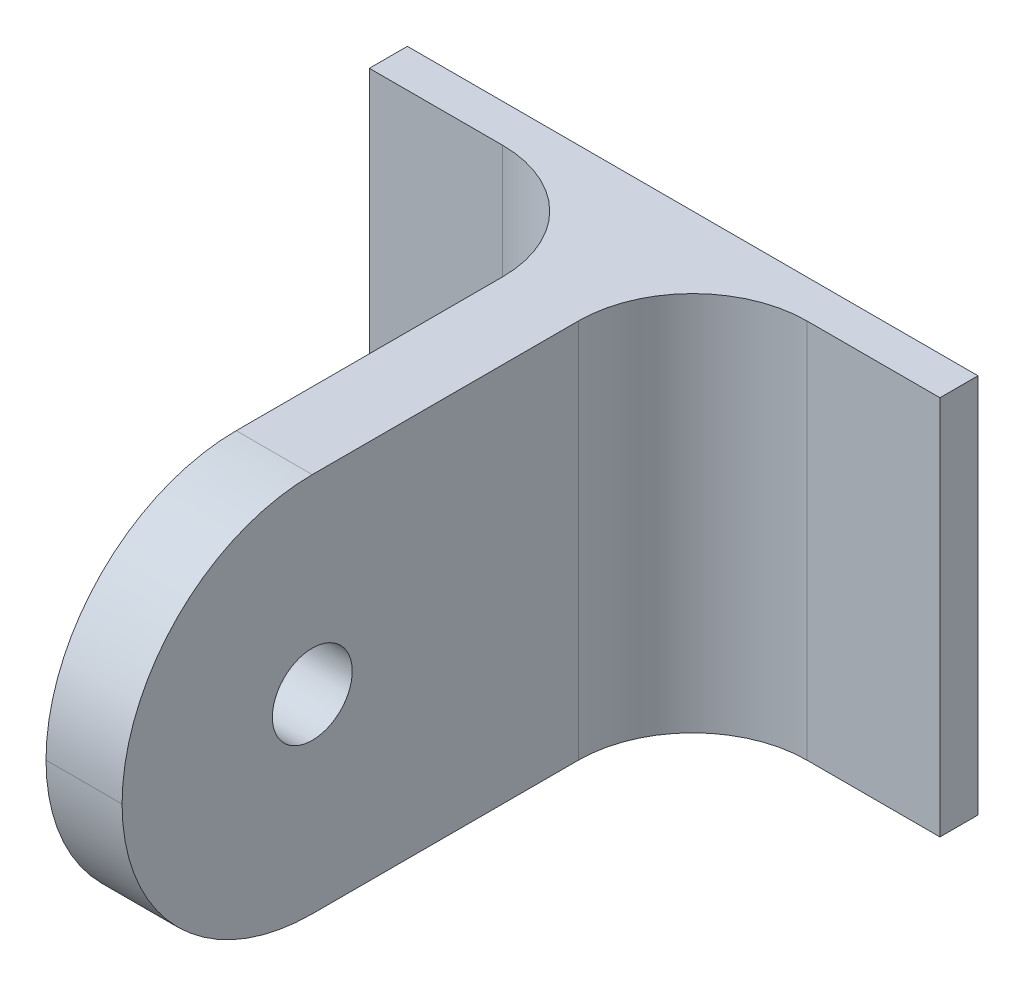
SolidWorks part; units mm, degrees
ref_plane "前视基准面" through (0, 0, 0) normal (0, 0, 1) x (1, 0, 0)
ref_plane "上视基准面" through (0, 0, 0) normal (0, 1, 0) x (1, 0, 0)
ref_plane "右视基准面" through (0, 0, 0) normal (1, 0, 0) x (0, 0, -1)
sketch "草图4" plane through (0, 0, 0) normal (0, 0, 1) x (1, 0, 0)
  line L1 (-24.0566, -2.8302) -> (5.9434, -2.8302)
  line L2 (-24.0566, -2.8302) -> (-24.0566, -22.8302)
  line L3 (-24.0566, -22.8302) -> (5.9434, -22.8302)
  line L4 (5.9434, -2.8302) -> (5.9434, -22.8302)
  dimension "D1" = 30
  dimension "D2" = 20
extrude "凸台-拉伸1" add sketch "草图4" along normal blind 2
sketch "草图5" plane through (0, 0, 2) normal (0, 0, 1) x (1, 0, 0)
  line L0 (5.9434, -2.8302) -> (-24.0566, -2.8302) construction
  line L1 (-11.0566, -2.8302) -> (-7.0566, -2.8302)
  line L2 (-11.0566, -2.8302) -> (-11.0566, -22.8302)
  line L3 (-11.0566, -22.8302) -> (-7.0566, -22.8302)
  line L4 (-7.0566, -2.8302) -> (-7.0566, -22.8302)
  line L5 (-24.0566, -22.8302) -> (5.9434, -22.8302) construction
  line L6 (-24.0566, -2.8302) -> (-24.0566, -22.8302) construction
  dimension "D1" = 4
  dimension "D2" = 13
extrude "凸台-拉伸2" add sketch "草图5" along normal blind 30
fillet "圆角1" radius 10 2 edges at (-9.0566, -2.8302, 32) (-9.0566, -22.8302, 32)
sketch "草图6" plane through (-11.0566, 0, 0) normal (-1, 0, 0) x (0, 0, 1)
  circle A0 centre (22, -12.8302) radius 2.1
  dimension "D1" = 4.2
extrude "切除-拉伸2" cut sketch "草图6" against normal blind 30
fillet "圆角2" radius 6 2 edges at (-11.0566, -12.8302, 2) (-7.0566, -12.8302, 2)
